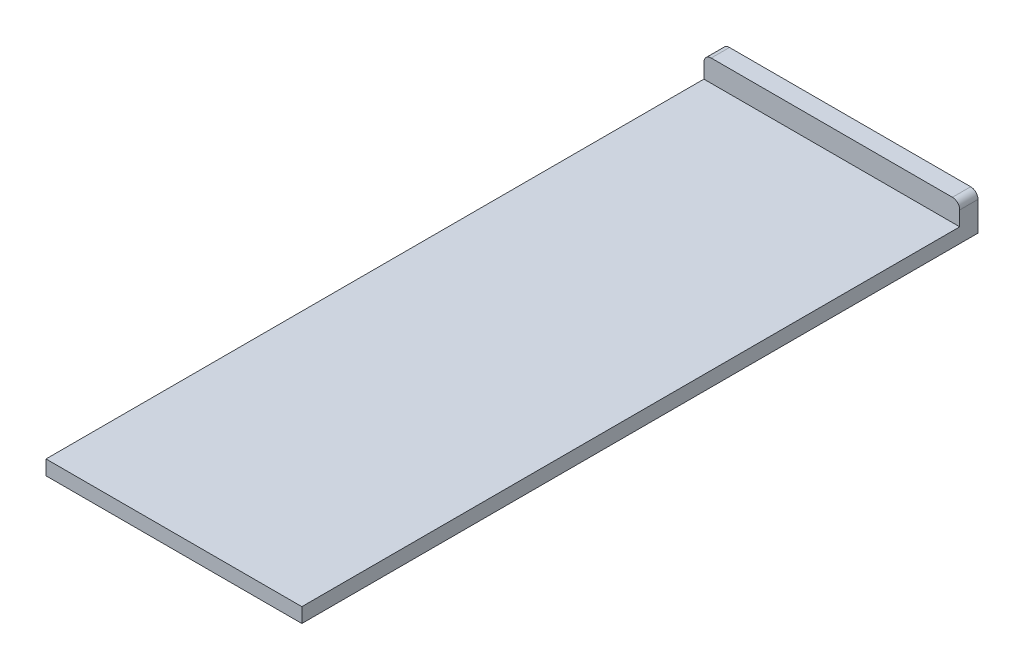
SolidWorks part; units mm, degrees
material "Custom Plastic"
ref_plane "Front Plane" through (0, 0, 0) normal (0, 0, 1) x (1, 0, 0)
ref_plane "Top Plane" through (0, 0, 0) normal (0, 1, 0) x (1, 0, 0)
ref_plane "Right Plane" through (0, 0, 0) normal (1, 0, 0) x (0, 0, -1)
sketch "Sliding Door Sketch" plane through (0, 0, 0) normal (0, 0, 1) x (1, 0, 0)
  line L0 (-44.9118, 0.127) -> (-44.9118, 10.287)
  line L1 (-42.3718, 12.827) -> (41.4482, 12.827)
  line L2 (43.9882, 10.287) -> (43.9882, 0.127)
  line L3 (43.9882, 0.127) -> (-44.9118, 0.127)
  line L4 (-44.9118, 5.207) -> (43.9882, 5.207)
  arc A0 (43.9882, 10.287) -> (41.4482, 12.827) centre (41.4482, 10.287) ccw
  arc A1 (-44.9118, 10.287) -> (-42.3718, 12.827) centre (-42.3718, 10.287) cw
  point P8 (43.9882, 12.827)
  point P11 (-44.9118, 12.827)
  dimension "D3" = 2.54
  dimension "D1" = 12.7
  dimension "D2" = 88.9
extrude "Sliding Door Holder" add sketch "Sliding Door Sketch" along normal blind 6.35 contours L4 L0 L3 L2 | A1 L0 L4 L2 A0 L1 region at (-0.4618, 2.667, 0) region at (-0.4618, 9.0037, 0)
extrude "Sliding Door" add sketch "Sketch1<5>" along normal blind 234.95 contours L4 L0 L3 L2 region at (-0.4618, 2.667, 0)
sketch "Sketch1<5>" plane through (0, 0, 0) normal (0, 0, 1) x (1, 0, 0) same geometry as "Sliding Door Sketch"
